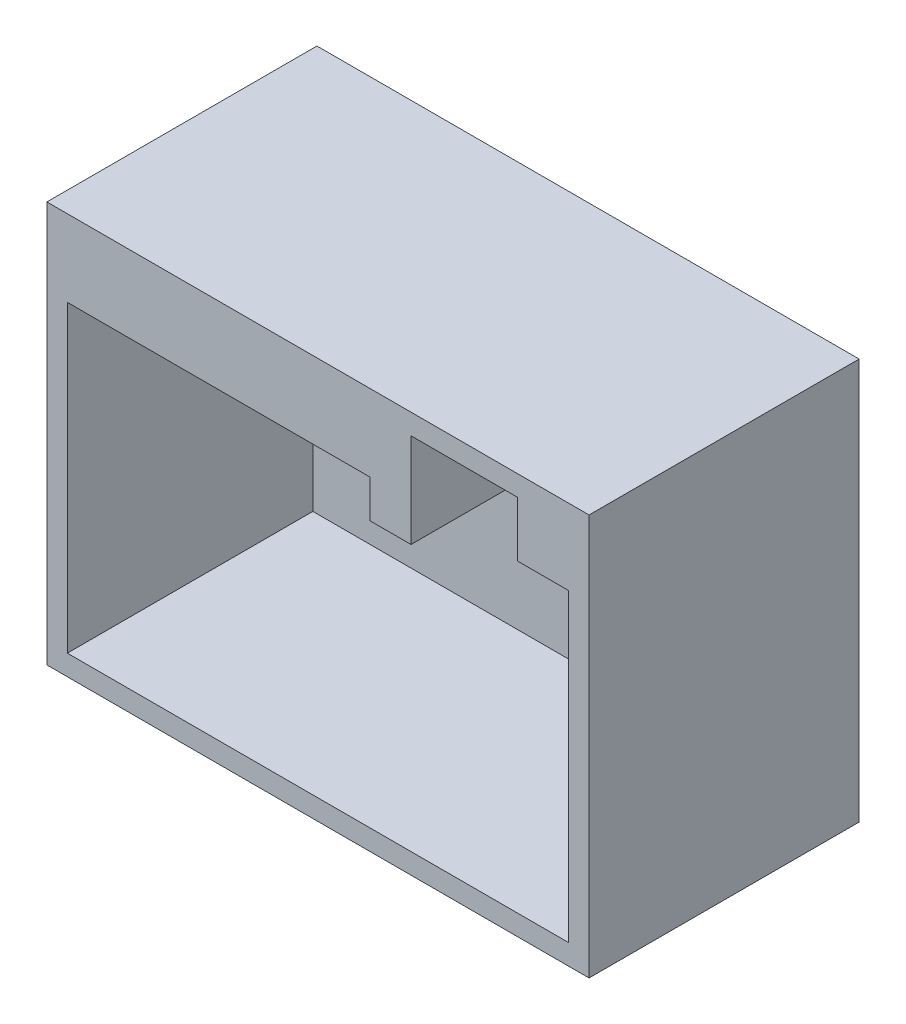
SolidWorks part; units mm, degrees
material "Ceramic Porcelain"
ref_plane "Front Plane" through (0, 0, 0) normal (0, 0, 1) x (1, 0, 0)
ref_plane "Top Plane" through (0, 0, 0) normal (0, 1, 0) x (1, 0, 0)
ref_plane "Right Plane" through (0, 0, 0) normal (1, 0, 0) x (0, 0, -1)
sketch "Sketch1" plane through (0, 0, 0) normal (0, 0, 1) x (1, 0, 0)
  line L0 (5588, 4470.4) -> (5588, 3784.6)
  line L1 (0, 0) -> (6223, 0)
  line L2 (0, 0) -> (0, 4470.4)
  line L3 (0, 4470.4) -> (6223, 4470.4)
  line L4 (6223, 0) -> (6223, 4470.4)
  line L5 (5588, 3784.6) -> (6223, 3784.6)
  line L6 (4267.2, 4470.4) -> (4267.2, 3302)
  line L7 (4267.2, 3302) -> (3759.2, 3302)
  line L8 (3759.2, 3302) -> (3759.2, 4470.4)
  line L9 (3759.2, 3771.9) -> (0, 3771.9)
  line L10 (3759.2, 3149.6) -> (609.6, 3149.6) construction
  line L11 (609.6, 3149.6) -> (609.6, 0) construction
  line L12 (3759.2, 3149.6) -> (3759.2, 3302) construction
  dimension "D1" = 6223
  dimension "D2" = 4470.4
  dimension "D3" = 685.8
  dimension "D4" = 635
  dimension "D5" = 1168.4
  dimension "D6" = 1955.8
  dimension "D7" = 508
  dimension "D8" = 469.9
  dimension "D9" = 609.6
  dimension "D10" = 622.3
extrude "Extrude-Thin1" add sketch "Sketch1" along normal blind 3048 and the other way blind 304.8 thin contours L1 L4 L3 L2 thin type one direction wall 254
extrude "Boss-Extrude1" add sketch "Sketch1<4>" against normal up to surface (304.8 mm away) contours L8 L9 L2 L1 L4 L5 L0 L3 L6 L7 | L9 L8 L3 L2 | L8 L7 L6 L3 | L0 L5 L4 L3 region at (5905.5, 4127.5, 0) region at (3172.8621, 1955.6101, 0) region at (4013.2, 3886.2, 0) region at (1879.6, 4121.15, 0) up to face at (3111.5, 2235.2, -304.8)
sketch "Sketch1<4>" plane through (0, 0, 0) normal (0, 0, 1) x (1, 0, 0) same geometry as "Sketch1"
extrude "Boss-Extrude2" add sketch "Sketch1<5>" along normal up to surface (3048 mm away) contours L9 L8 L3 L2 | L8 L7 L6 L3 | L0 L5 L4 L3 region at (5905.5, 4127.5, 0) region at (4013.2, 3886.2, 0) region at (1879.6, 4121.15, 0) up to face at (3111.5, 2235.2, 3048)
sketch "Sketch1<5>" plane through (0, 0, 0) normal (0, 0, 1) x (1, 0, 0) same geometry as "Sketch1"
